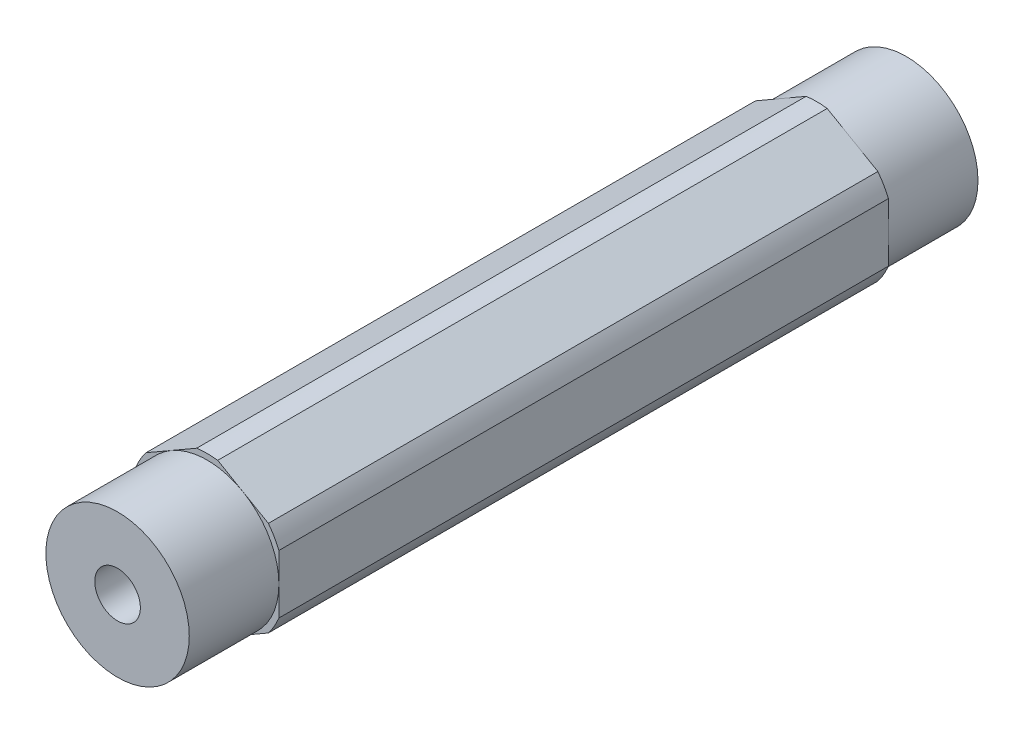
SolidWorks part; units mm, degrees
material "6061-T6 (SS)"
ref_plane "Front Plane" through (0, 0, 0) normal (0, 0, 1) x (1, 0, 0)
ref_plane "Top Plane" through (0, 0, 0) normal (0, 1, 0) x (1, 0, 0)
ref_plane "Right Plane" through (0, 0, 0) normal (1, 0, 0) x (0, 0, -1)
sketch "Sketch1" plane through (0, 0, 0) normal (0, 0, 1) x (1, 0, 0)
  line L1 (0, 7.3323) -> (-6.35, 3.6662)
  line L2 (-6.35, 3.6662) -> (-6.35, -3.6662)
  line L3 (-6.35, -3.6662) -> (0, -7.3323)
  line L4 (0, -7.3323) -> (6.35, -3.6662)
  line L5 (6.35, -3.6662) -> (6.35, 3.6662)
  line L6 (6.35, 3.6662) -> (0, 7.3323)
  circle A0 centre (0, 0) radius 6.35 construction
  circle A1 centre (0, 0) radius 6.858
  circle A2 centre (0, 0) radius 2.0193
  dimension "D1" = 12.7
  dimension "D2" = 13.716
  dimension "D3" = 4.0386
extrude "Boss-Extrude1" add sketch "Sketch1" along normal mid plane 53.975 contours L5 A1 L6 L1 L2 L3 L4 region at (0, 6.6711, 0)
sketch "Sketch2" plane through (0, 0, 26.9875) normal (0, 0, 1) x (1, 0, 0)
  circle A0 centre (0, 0) radius 6.35
  circle A1 centre (0, 0) radius 2.0193
  dimension "D1" = 12.7
  dimension "D2" = 4.0386
extrude "Boss-Extrude2" add sketch "Sketch2" along normal blind 7.9375
mirror "Mirror1" about plane through (0, 0, 0) normal (0, 0, 1) of "Boss-Extrude2"
